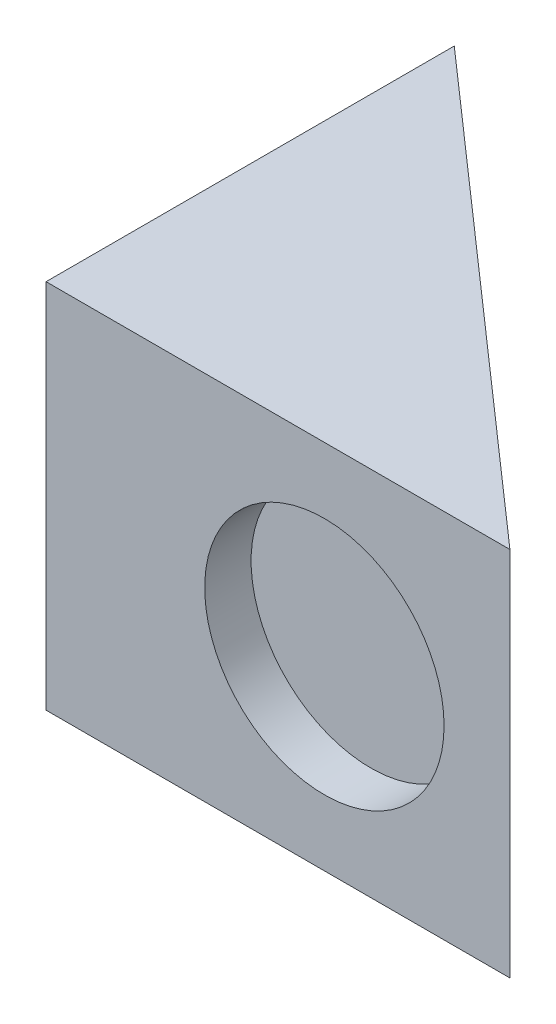
SolidWorks part; units mm, degrees
ref_plane "Front Plane" through (0, 0, 0) normal (0, 0, 1) x (1, 0, 0)
ref_plane "Top Plane" through (0, 0, 0) normal (0, 1, 0) x (1, 0, 0)
ref_plane "Right Plane" through (0, 0, 0) normal (1, 0, 0) x (0, 0, -1)
sketch "Sketch1" plane through (0, 0, 0) normal (0, 1, 0) x (1, 0, 0)
  line L0 (0, 0) -> (0, 27.94)
  line L1 (0, 27.94) -> (31.75, 0)
  line L2 (31.75, 0) -> (0, 0)
  dimension "D1" = 27.94
  dimension "D2" = 31.75
extrude "Boss-Extrude1" add sketch "Sketch1" along normal blind 25.4
sketch "Sketch2" plane through (0, 0, 0) normal (0, 0, 1) x (1, 0, 0)
  line L0 (0, 25.4) -> (31.75, 25.4) construction
  line L2 (31.75, 25.4) -> (31.75, 0) construction
  circle A0 centre (19.05, 12.7) radius 8.1915
  dimension "D3" = 16.383
  dimension "D1" = 12.7
  dimension "D2" = 12.7
extrude "Cut-Extrude1" cut sketch "Sketch2" against normal blind 3.175 contours A0
sketch "Sketch3" plane through (0, 0, 0) normal (-1, 0, 0) x (0, 0, 1)
  line L2 (-27.94, 25.4) -> (0, 25.4) construction
  line L3 (0, 25.4) -> (0, 0) construction
  circle A0 centre (-9.652, 15.748) radius 8.1915
  dimension "D3" = 16.383
  dimension "D1" = 9.652
  dimension "D2" = 9.652
extrude "Cut-Extrude2" cut sketch "Sketch3" against normal blind 3.175
sketch "Sketch4" plane through (0, 0, 0) normal (-1, 0, 0) x (0, 0, 1)
  line L0 (-27.94, 25.4) -> (0, 25.4) construction
  line L1 (0, 25.4) -> (0, 0) construction
  circle A0 centre (-20.32, 6.35) radius 5.0165
  dimension "D1" = 10.033
  dimension "D2" = 19.05
  dimension "D3" = 20.32
extrude "Cut-Extrude3" cut sketch "Sketch4" against normal blind 1.6129
